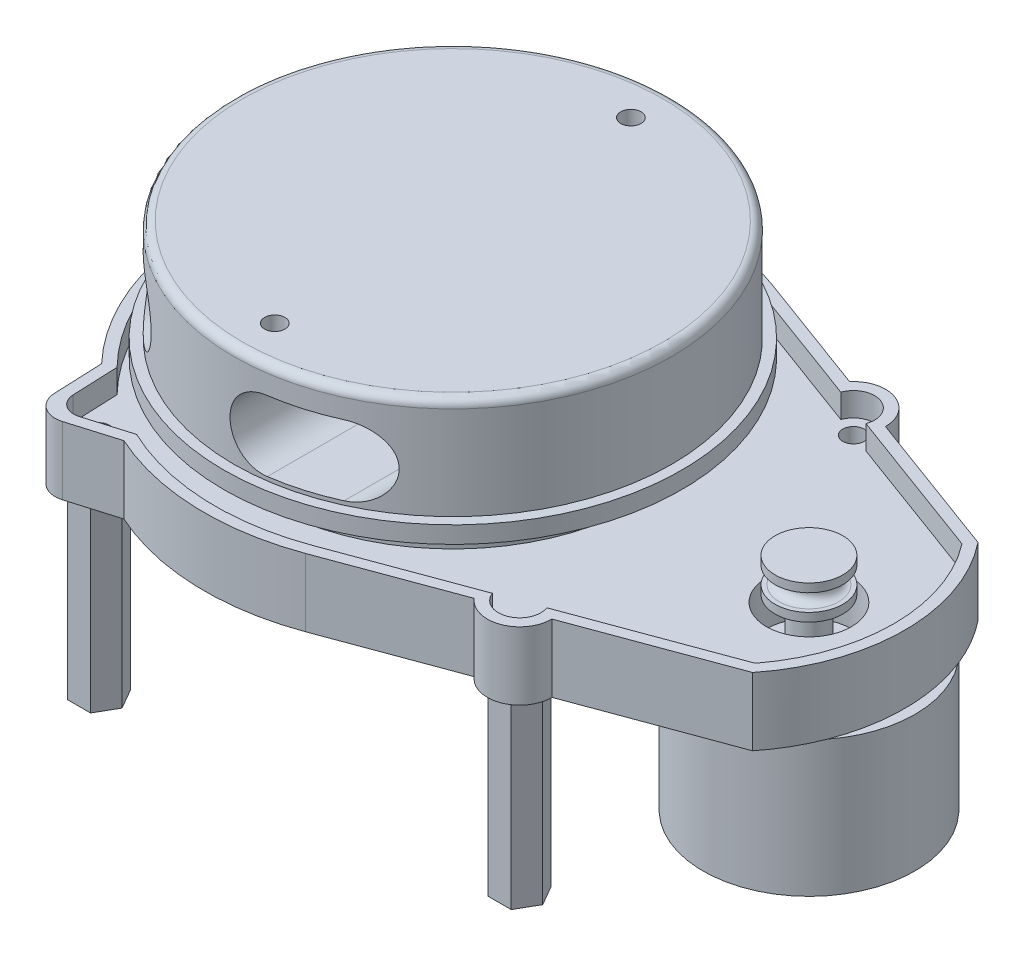
SolidWorks part; units mm, degrees
ref_plane "Front Plane" through (0, 0, 0) normal (0, 0, 1) x (1, 0, 0)
ref_plane "Top Plane" through (0, 0, 0) normal (0, 1, 0) x (1, 0, 0)
ref_plane "Right Plane" through (0, 0, 0) normal (1, 0, 0) x (0, 0, -1)
sketch "Sketch2" plane through (0, 0, 0) normal (0, 1, 0) x (1, 0, 0)
  line L0 (66.04, 0) -> (-35.56, 0)
  line L1 (37.9801, 23.8951) -> (60.7691, 15.4913)
  line L2 (12.3034, 33.3638) -> (32.0223, 26.0921)
  line L3 (-25.4, 24.8868) -> (-24.9746, 35.0379)
  line L4 (-24.9746, 35.0379) -> (-15.24, 32.1287)
  arc A0 (12.3034, 33.3638) -> (-15.24, 32.1287) centre (0, 0) ccw
  arc A1 (60.7691, 15.4913) -> (66.04, 0) centre (40.64, 0) cw
  arc A2 (37.9801, 23.8951) -> (32.0223, 26.0921) centre (35.0012, 24.9936) ccw
  arc A3 (-25.4, 24.8868) -> (-35.56, 0) centre (0, 0) ccw
  dimension "D1" = 35.56
  dimension "D4" = 25.4
  dimension "D3" = 6.35
  dimension "D2" = 66.04
  dimension "D5" = 24.9936
  dimension "D6" = 35.0012
  dimension "D7" = 10.16
  dimension "D8" = 10.16
  dimension "D9" = 10.16
extrude "Boss-Extrude2" add sketch "Sketch2" along normal blind 6.604 separate body
sketch "Sketch12" plane through (0, 0, 0) normal (0, 1, 0) x (1, 0, 0)
  line L0 (-35.56, 0) -> (-37.211, 0)
  line L1 (66.04, 0) -> (67.691, 0)
  line L10 (31.3177, 28.1116) -> (12.8746, 34.9128)
  line L11 (-15.3668, 33.8898) -> (-26.5353, 37.2275)
  line L12 (-26.5353, 37.2275) -> (-27.0233, 25.5812)
  line L13 (-37.1744, -1.651) -> (67.6406, -1.651)
  line L14 (61.7794, 16.8784) -> (39.8272, 24.9736)
  line L15 (31.3177, 28.1116) -> (12.8746, 34.9128)
  line L16 (-15.3668, 33.8898) -> (-26.5353, 37.2275)
  line L17 (-26.5353, 37.2275) -> (-27.0233, 25.5812)
  line L19 (61.7794, 16.8784) -> (39.8272, 24.9736)
  line L25 (32.0223, 26.0921) -> (12.3034, 33.3638)
  line L26 (-15.24, 32.1287) -> (-24.9746, 35.0379)
  line L27 (-24.9746, 35.0379) -> (-25.4, 24.8868)
  line L28 (-35.56, 0) -> (66.04, 0)
  line L29 (60.7691, 15.4913) -> (37.9801, 23.8951)
  line L30 (32.0223, 26.0921) -> (12.3034, 33.3638)
  line L31 (-15.24, 32.1287) -> (-24.9746, 35.0379)
  line L32 (-24.9746, 35.0379) -> (-25.4, 24.8868)
  line L34 (60.7691, 15.4913) -> (37.9801, 23.8951)
  arc A8 (39.8272, 24.9736) -> (31.3177, 28.1116) centre (35.0012, 24.9936) ccw
  arc A9 (12.8746, 34.9128) -> (-15.3668, 33.8898) centre (0, 0) ccw
  arc A10 (-27.0233, 25.5812) -> (-37.1744, -1.651) centre (0, 0) ccw
  arc A11 (67.6406, -1.651) -> (61.7794, 16.8784) centre (40.64, 0) ccw
  arc A12 (39.8272, 24.9736) -> (31.3177, 28.1116) centre (35.0012, 24.9936) ccw
  arc A13 (12.8746, 34.9128) -> (-15.3668, 33.8898) centre (0, 0) ccw
  arc A14 (-27.0233, 25.5812) -> (-37.211, 0) centre (0, 0) ccw
  arc A15 (67.691, 0) -> (61.7794, 16.8784) centre (40.64, 0) ccw
  arc A20 (37.9801, 23.8951) -> (32.0223, 26.0921) centre (35.0012, 24.9936) ccw
  arc A21 (12.3034, 33.3638) -> (-15.24, 32.1287) centre (0, 0) ccw
  arc A22 (-25.4, 24.8868) -> (-35.56, 0) centre (0, 0) ccw
  arc A23 (66.04, 0) -> (60.7691, 15.4913) centre (40.64, 0) ccw
  arc A24 (37.9801, 23.8951) -> (32.0223, 26.0921) centre (35.0012, 24.9936) ccw
  arc A25 (12.3034, 33.3638) -> (-15.24, 32.1287) centre (0, 0) ccw
  arc A26 (-25.4, 24.8868) -> (-35.56, 0) centre (0, 0) ccw
  arc A27 (66.04, 0) -> (60.7691, 15.4913) centre (40.64, 0) ccw
  dimension "D1" = 1.651
  dimension "D2" = 0
extrude "Boss-Extrude8" add sketch "Sketch12" along normal blind 10.16
fillet "Fillet2" radius 2.54 1 edges at (-24.9746, 8.382, -35.0379)
fillet "Fillet3" radius 3.302 1 edges at (-26.5353, 5.08, -37.2275)
sketch "Sketch4" plane through (0, 6.604, 0) normal (0, 1, 0) x (1, 0, 0)
  line L1 (-35.56, 0) -> (66.04, 0) construction
  circle A0 centre (35, 25) radius 1.6
  circle A1 centre (-22, 31.0007) radius 1.6
  dimension "D5" = 3.2
  dimension "D1" = 25
  dimension "D2" = 35
  dimension "D3" = 22
  dimension "D4" = 31.0007
extrude "Cut-Extrude1" cut sketch "Sketch4" against normal through all
ref_axis "Axis1" through (-22, 0, -31.0007) along (0, 1, 0)
ref_axis "Axis2" through (35, 0, -25) along (0, 1, 0)
sketch "Sketch15" plane through (0, 0, 0) normal (0, -1, 0) x (-1, 0, 0)
  line L0 (23.7304, 28.0035) -> (20.2696, 28.0035)
  line L1 (20.2696, 28.0035) -> (18.5391, 31.0007)
  line L2 (18.5391, 31.0007) -> (20.2696, 33.9979)
  line L3 (20.2696, 33.9979) -> (23.7304, 33.9979)
  line L4 (23.7304, 33.9979) -> (25.4609, 31.0007)
  line L5 (25.4609, 31.0007) -> (23.7304, 28.0035)
  line L6 (-33.2696, 22.0028) -> (-36.7304, 22.0028)
  line L7 (-36.7304, 22.0028) -> (-38.4609, 25)
  line L8 (-38.4609, 25) -> (-36.7304, 27.9972)
  line L9 (-36.7304, 27.9972) -> (-33.2696, 27.9972)
  line L10 (-33.2696, 27.9972) -> (-31.5391, 25)
  line L11 (-31.5391, 25) -> (-33.2696, 22.0028)
  point P6 (22, 28.0035)
  point P7 (22, 33.9979)
  point P14 (-35, 27.9972)
  point P17 (-35, 22.0028)
  dimension "D1" = 5.9944
  dimension "D2" = 120
  dimension "D3" = 120
extrude "Boss-Extrude10" add sketch "Sketch15" along normal blind 27.559
sketch "Sketch16" plane through (0, -27.559, 0) normal (0, -1, 0) x (-1, 0, 0)
  circle A0 centre (22, 31.0007) radius 1.6
  circle A1 centre (-35, 25) radius 1.6
  circle A2 centre (22, 31.0007) radius 1.6 construction
extrude "Cut-Extrude4" cut sketch "Sketch16" against normal through all
mirror "Mirror7" about plane through (66.04, 6.604, 0) normal (0, 0, -1) of "Cut-Extrude4", "Boss-Extrude8", "Fillet3", "Fillet2", "Boss-Extrude2", "Cut-Extrude1", "Boss-Extrude10"
sketch "Sketch13" plane through (0, 6.604, 0) normal (0, 1, 0) x (1, 0, 0)
  circle A0 centre (0, 0) radius 27.94
  dimension "D1" = 55.88
extrude "Boss-Extrude9" add sketch "Sketch13" along normal blind 5.08
sketch "Sketch10" plane through (0, 6.604, 0) normal (0, 1, 0) x (1, 0, 0)
  circle A0 centre (0, 0) radius 34.29
  dimension "D1" = 68.58
extrude "Boss-Extrude6" add sketch "Sketch10" along normal blind 2.54 from surface contours A0 starting at face at (0, 11.684, 27.94)
sketch "Sketch5" plane through (0, 6.604, 0) normal (0, 1, 0) x (1, 0, 0)
  circle A0 centre (0, 0) radius 32.7914
  dimension "D1" = 65.5828
extrude "Boss-Extrude3" add sketch "Sketch5" along normal blind 15.24 from surface starting at face at (0, 14.224, 34.29)
fillet "Fillet5" radius 1.27 1 edges at (0, 29.464, 32.7914)
sketch "Sketch8" plane through (0, 29.464, 0) normal (0, 1, 0) x (1, 0, 0)
  circle A0 centre (0, 26.67) radius 1.524
  circle A1 centre (0, -26.67) radius 1.524
  dimension "D1" = 26.67
  dimension "D2" = 3.048
  dimension "D3" = 26.67
extrude "Cut-Extrude2" cut sketch "Sketch8" against normal blind 2.54
sketch "Sketch9" plane through (0, 0, 0) normal (0, 0, 1) x (1, 0, 0)
  line L0 (4.6736, 20.066) -> (13.5636, 20.066) construction
  line L1 (4.6736, 25.3238) -> (13.5636, 25.3238)
  line L2 (4.6736, 14.8082) -> (13.5636, 14.8082)
  line L4 (32.7914, 29.464) -> (-32.7914, 29.464) construction
  line L5 (-32.7914, 28.194) -> (-32.7914, 14.224) construction
  circle A0 centre (-22.6314, 20.066) radius 5.2578
  arc A1 (4.6736, 25.3238) -> (4.6736, 14.8082) centre (4.6736, 20.066) ccw
  arc A2 (13.5636, 14.8082) -> (13.5636, 25.3238) centre (13.5636, 20.066) ccw
  point P4 (9.1186, 20.066)
  dimension "D1" = 10.5156
  dimension "D4" = 10.16
  dimension "D2" = 9.398
  dimension "D3" = 31.75
  dimension "D5" = 8.89
extrude "Cut-Extrude3" cut sketch "Sketch9" along normal through all
sketch "Sketch19" plane through (0, 6.604, 0) normal (0, 1, 0) x (1, 0, 0)
  circle A0 centre (53.34, 0) radius 6.35
  dimension "D2" = 12.7
  dimension "D1" = 53.34
extrude "Cut-Extrude5" cut sketch "Sketch19" against normal through all
sketch "Sketch7" plane through (0, 0, 0) normal (0, -1, 0) x (1, 0, 0)
  circle A0 centre (53.34, 0) radius 15.875
  circle A2 centre (53.34, 0) radius 6.35 construction
  dimension "D1" = 31.75
extrude "Boss-Extrude5" add sketch "Sketch7" along normal blind 20.32
sketch "Sketch20" plane through (0, 0, 0) normal (0, 1, 0) x (1, 0, 0)
  circle A0 centre (53.34, 0) radius 2.54
  circle A1 centre (53.34, 0) radius 6.35 construction
  dimension "D1" = 5.08
extrude "Boss-Extrude13" add sketch "Sketch20" along normal blind 7.62
sketch "Sketch6" plane through (0, 6.604, 0) normal (0, 1, 0) x (1, 0, 0)
  circle A0 centre (53.34, 0) radius 5.08
  dimension "D1" = 10.16
  dimension "D2" = 53.34
extrude "Boss-Extrude4" add sketch "Sketch6" along normal blind 1.27 from surface starting at face at (53.34, 7.62, 2.54)
sketch "Sketch17" plane through (0, 8.89, 0) normal (0, 1, 0) x (1, 0, 0)
  circle A0 centre (53.34, 0) radius 3.175
  circle A1 centre (53.34, 0) radius 5.08 construction
  dimension "D1" = 6.35
extrude "Boss-Extrude11" add sketch "Sketch17" along normal blind 2.54
sketch "Sketch18" plane through (0, 11.43, 0) normal (0, 1, 0) x (1, 0, 0)
  circle A0 centre (53.34, 0) radius 5.08
  circle A1 centre (53.34, 0) radius 5.08 construction
extrude "Boss-Extrude12" add sketch "Sketch18" along normal blind 1.27
fillet "Fillet4" radius 1.27 2 edges at (53.34, 11.43, 3.175) (53.34, 8.89, 3.175)
